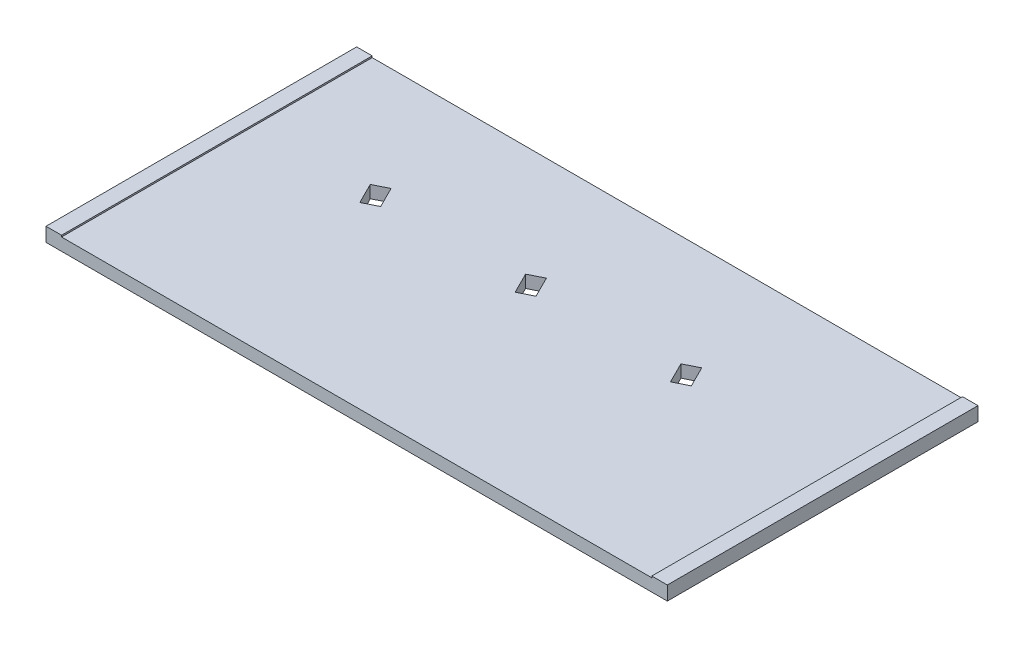
SolidWorks part; units mm, degrees
ref_plane "Front Plane" through (0, 0, 0) normal (0, 0, 1) x (1, 0, 0)
ref_plane "Top Plane" through (0, 0, 0) normal (0, 1, 0) x (1, 0, 0)
ref_plane "Right Plane" through (0, 0, 0) normal (1, 0, 0) x (0, 0, -1)
sketch "Sketch1" plane through (0, 0, 0) normal (0, 1, 0) x (1, 0, 0)
  line L1 (-50.8, -25.4) -> (50.8, -25.4)
  line L2 (-50.8, -25.4) -> (-50.8, 25.4)
  line L3 (-50.8, 25.4) -> (50.8, 25.4)
  line L4 (50.8, -25.4) -> (50.8, 25.4)
  line L5 (0, 25.4) -> (0, -25.4) construction
  line L6 (-50.8, 0) -> (50.8, 0) construction
  point P0 (0, 0)
  dimension "D1" = 50.8
  dimension "D2" = 101.6
extrude "Boss-Extrude1" add sketch "Sketch1" along normal blind 2.032
sketch "Sketch2" plane through (0, 2.032, 0) normal (0, 1, 0) x (1, 0, 0)
  line L0 (-3.3577, 3.8746) -> (-1.0859, 5.0107)
  line L1 (-3.3577, 3.8746) -> (-5.0618, 7.2822)
  line L2 (-1.0859, 5.0107) -> (-2.7901, 8.4183)
  line L3 (-5.0618, 7.2822) -> (-2.7901, 8.4183)
  line L5 (-1.2573, 0) -> (1.2573, 0) construction
  circle A0 centre (0, 0) radius 5.127 construction
  dimension "D1" = 10.254
  dimension "D3" = 3.81
  dimension "D4" = 2.54
  dimension "D2" = 63.43
extrude "Cut-Extrude1" cut sketch "Sketch2" against normal through all contours L3 L1 L0 L2 region at (-3.0739, 2.032, -6.1464)
sketch "Sketch3" plane through (0, 2.032, 0) normal (0, 1, 0) x (1, 0, 0)
  line L0 (-7.112, 8.89) -> (-2.032, 8.89)
  line L1 (-7.112, 8.89) -> (-7.112, 11.43)
  line L2 (-2.032, 8.89) -> (-2.032, 11.43)
  line L3 (-7.112, 11.43) -> (-2.032, 11.43)
  line L4 (-1.2573, 0) -> (1.2573, 0) construction
  line L5 (0, -1.2573) -> (0, 1.2573) construction
  dimension "D1" = 2.54
  dimension "D2" = 5.08
  dimension "D3" = 2.032
  dimension "D4" = 8.89
pattern_linear "LPattern1" count 2 spacing 25.4 along (-1, 0, 0) count 2 spacing 25.4 along (1, 0, 0) of "Cut-Extrude1"
sketch "Sketch4" plane through (0, 2.032, 0) normal (0, 1, 0) x (1, 0, 0)
  line L0 (-50.8, -25.4) -> (50.8, -25.4) construction
  line L1 (-50.8, 25.4) -> (-48.26, 25.4)
  line L2 (-50.8, 25.4) -> (-50.8, -25.4)
  line L3 (-50.8, -25.4) -> (-48.26, -25.4)
  line L4 (-48.26, 25.4) -> (-48.26, -25.4)
  line L6 (50.8, 25.4) -> (48.26, 25.4)
  line L7 (50.8, 25.4) -> (50.8, -25.4)
  line L8 (50.8, -25.4) -> (48.26, -25.4)
  line L9 (48.26, 25.4) -> (48.26, -25.4)
  line M10 (50.8, -25.4) -> (50.8, 25.4)
  line M11 (50.8, 25.4) -> (-50.8, 25.4)
  line M12 (-50.8, 25.4) -> (-50.8, -25.4)
  line M13 (-50.8, -25.4) -> (50.8, -25.4)
  dimension "D1" = 2.54
extrude "Boss-Extrude2" add sketch "Sketch4" along normal blind 0.254 contours L4 M11 M12 M13 | L9 M11 M13 M10 | L2 L1 L4 L3 region at (-49.53, 2.032, 0) region at (49.53, 2.032, 0)
equation "\"Arrow Height\"= 1in"
equation "\"Button Height\"= 2in"
equation "\"Button Width\"= 4in"
equation "\"Haptic Diameter\"= 10mm"
equation "\"Haptic Thickness\"= 2.7mm"
equation "\"D1@Sketch1\"=\"Button Height\""
equation "\"D2@Sketch1\"=\"Button Width\""
equation "\"D1@Sketch2\"=\"Haptic Diameter\"+.01in"
equation "\"Arrow Spacing\"= 1in"
equation "\"Arrow Width\" = 0.75in"
equation "\"Haptic Wire Angle\" = 63.43"
equation "\"Haptic Wire Width\" = .1in"
equation "\"Hatic Wire Height\" = .15in"
equation "\"D2@Sketch2\"=\"Haptic Wire Angle\""
equation "\"D4@Sketch2\"=\"Haptic Wire Width\""
equation "\"D3@Sketch2\"=\"Hatic Wire Height\""
